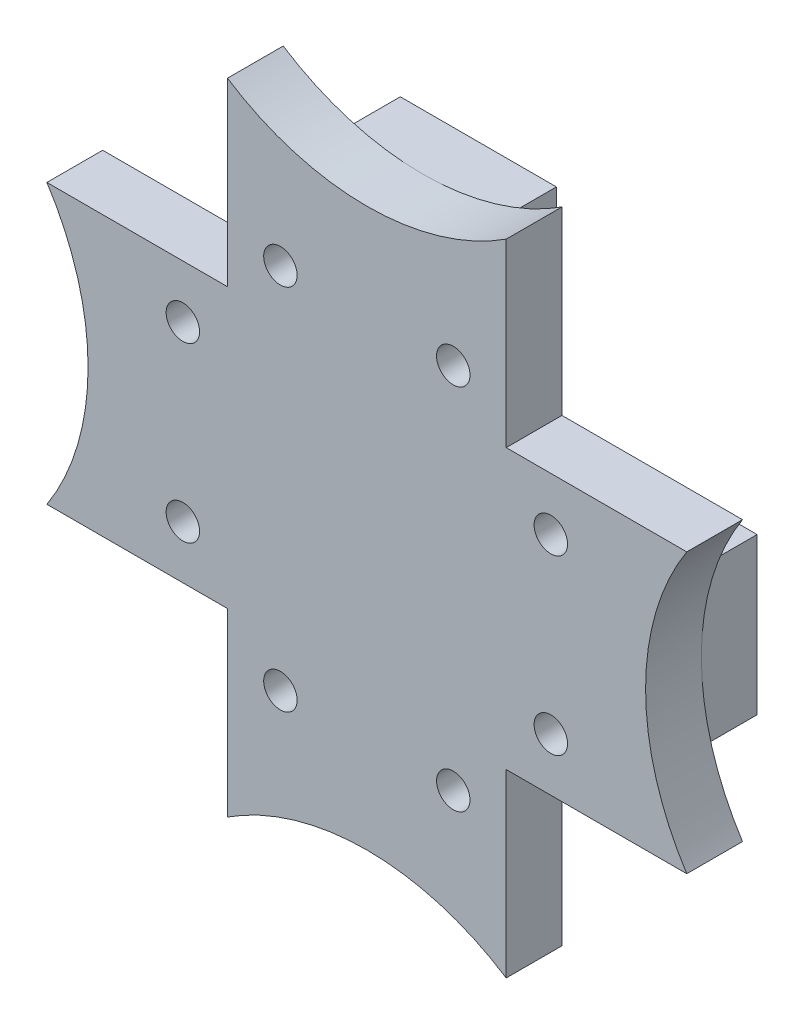
SolidWorks part; units mm, degrees
ref_plane "Top Plane" through (0, 0, 0) normal (0, 0, 1) x (1, 0, 0)
ref_plane "Right Plane" through (0, 0, 0) normal (0, 1, 0) x (1, 0, 0)
ref_plane "Front Plane" through (0, 0, 0) normal (1, 0, 0) x (0, 0, -1)
sketch "Sketch1" plane through (0, 0, 0) normal (0, 0, 1) x (1, 0, 0)
  line L0 (7.5, 4) -> (7.5, 0)
  line L1 (7.5, 0) -> (-7.5, 0)
  line L2 (-7.5, 0) -> (-7.5, 4)
  line L3 (-7.5, 4) -> (-3.0025, 4)
  line L4 (-3.0025, 4) -> (-3.0025, 12)
  line L5 (-3.0025, 12) -> (3.0025, 12)
  line L6 (3.0025, 12) -> (3.0025, 4)
  line L7 (3.0025, 4) -> (7.5, 4)
  line L8 (7.5, 0) -> (12.5, 0)
  line L10 (12.5, 0) -> (12.5, 12)
  line L11 (12.5, 12) -> (3.0025, 12)
  line L12 (-3.0025, 12) -> (-12.5, 12)
  line L13 (-12.5, 12) -> (-12.5, 0)
  line L15 (-12.5, 0) -> (-7.5, 0)
  line L16 (-7.7512, 8.5) -> (7.7512, 8.5) construction
  line L18 (0, 0) -> (0, 8.5) construction
  circle A0 centre (7.7512, 8.5) radius 1.5
  circle A1 centre (-7.7512, 8.5) radius 1.5
  dimension "D3" = 3
  dimension "D1" = 15
  dimension "D2" = 25
  dimension "D4" = 3.5
  dimension "D5" = 4.7488
  dimension "D6" = 12
  dimension "D7" = 4
  dimension "D8" = 4.4975
sketch "Sketch2" plane through (0, 0, 0) normal (0, 0, 1) x (1, 0, 0)
  line L1 (-12.5, -3.6933) -> (12.5, -3.6933) construction
  line L2 (-12.5, -3.6933) -> (-12.5, 25)
  line L3 (-12.5, 25) -> (12.5, 25)
  line L4 (12.5, -3.6933) -> (12.5, 25)
  arc A0 (-12.5, -3.6933) -> (12.5, -3.6933) centre (0, -23) cw
  circle A1 centre (-7.7512, 8.5) radius 1.5
  circle A2 centre (7.7512, 8.5) radius 1.5
  circle A3 centre (-7.7512, 8.5) radius 1.5 construction
  circle A4 centre (7.7512, 8.5) radius 1.5 construction
  dimension "D1" = 23
  dimension "D2" = 25
extrude "Boss-Extrude1" add sketch "Sketch2" along normal blind 5
sketch "Sketch3" plane through (0, 0, 0) normal (0, 0, -1) x (-1, 0, 0)
  line L8 (2.5025, 11.5) -> (2.5025, 25)
  line L9 (-12.5, 25) -> (12.5, 25) construction
  line L10 (2.5025, 25) -> (-2.5025, 25)
  line L11 (-2.5025, 25) -> (-2.5025, 11.5)
  line L12 (7, 0.5) -> (7, 0)
  line L13 (7, 0) -> (-7, 0)
  line L14 (-7, 0) -> (-7, 0.5)
  line L15 (7, 3) -> (2.5025, 3)
  line L16 (-7, 0.5) -> (7, 0.5)
  line L17 (-7, 3.5) -> (-7, 0.5)
  line L18 (-2.5025, 3.5) -> (-7, 3.5)
  line L19 (-2.5025, 11.5) -> (-2.5025, 3.5)
  line L20 (2.5025, 11.5) -> (-2.5025, 11.5)
  line L21 (2.5025, 3.5) -> (2.5025, 11.5)
  line L22 (7, 3.5) -> (2.5025, 3.5)
  line L23 (7, 0.5) -> (7, 3.5)
  line L24 (-7, 0.5) -> (7, 0.5) construction
  line L25 (-7, 3) -> (-7, 0.5)
  line L26 (-2.5025, 3.5) -> (-7, 3.5) construction
  line L27 (-2.5025, 11.5) -> (-2.5025, 3.5)
  line L29 (2.5025, 3.5) -> (2.5025, 11.5)
  line L30 (7, 3.5) -> (2.5025, 3.5) construction
  line L31 (7, 0.5) -> (7, 3)
  line L32 (2.5025, 3) -> (2.5025, 3.5)
  line L33 (-2.5025, 3.5) -> (-2.5025, 3)
  line L34 (-2.5025, 3) -> (-7, 3)
  line L35 (7, 3) -> (7, 3.5) construction
  line L36 (-7, 3.5) -> (-7, 3) construction
  dimension "D1" = 0.5
extrude "Boss-Extrude2" add sketch "Sketch3" along normal blind 5
ref_axis "Axis1" through (0, 25, 5) along (0, 0, -1)
ref_plane "Plane1" through (12.5, 12.5, 0) normal (0.7071, 0.7071, 0) x (0, 0, -1)
mirror "Mirror1" about plane through (-12.5, 25, 5) normal (0, -1, 0) of bodies 103
mirror "Mirror2" about plane through (12.5, 12.5, 0) normal (0.7071, 0.7071, 0) of bodies 114
